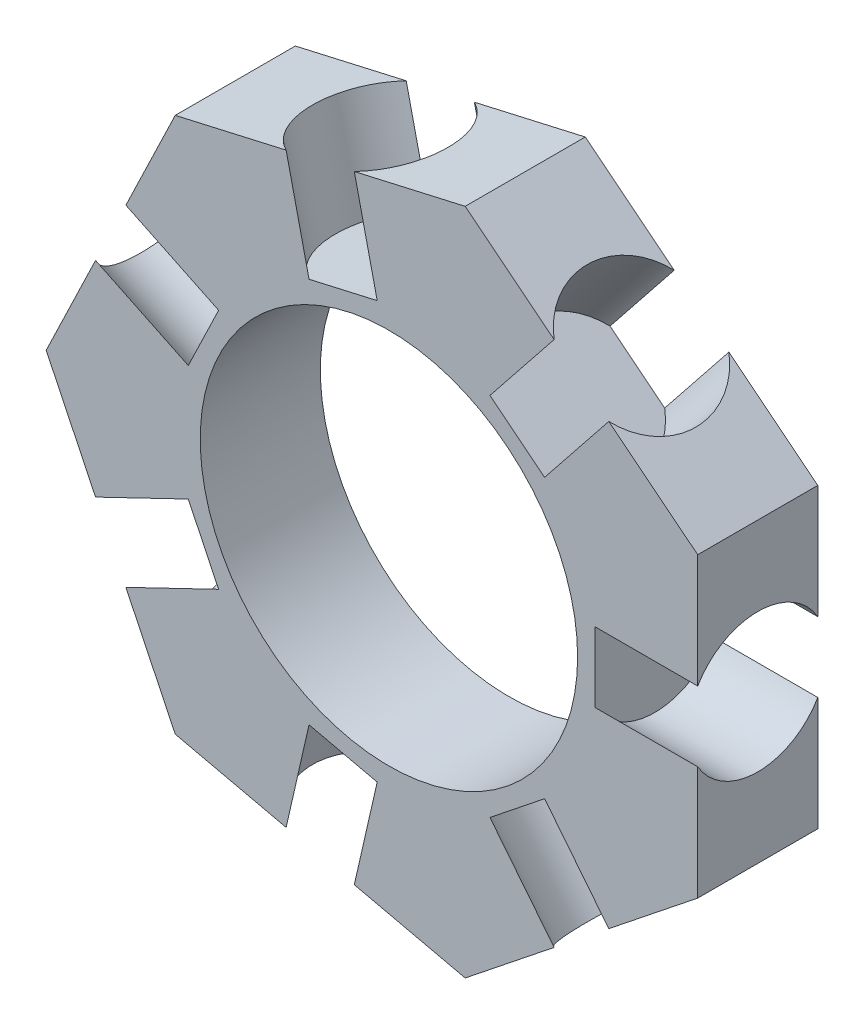
SolidWorks part; units mm, degrees
ref_plane "Top Plane" through (0, 0, 0) normal (0, 0, 1) x (1, 0, 0)
ref_plane "Right Plane" through (0, 0, 0) normal (0, 1, 0) x (1, 0, 0)
ref_plane "Front Plane" through (0, 0, 0) normal (1, 0, 0) x (0, 0, -1)
ref_axis "x-axis" through (-88.99, 0, 0) along (1, 0, 0)
ref_axis "y-axis" through (0, -55, 0) along (0, 1, 0)
ref_axis "z-axis" through (0, 0, 55) along (0, 0, -1)
sketch "Sketch1" plane through (0, 0, 0) normal (0, 0, 1) x (1, 0, 0)
  line L8 (-19.9785, 0) -> (0, 0) construction
  line L9 (-19.9785, 0) -> (-12.4564, -15.6198)
  line L10 (-12.4564, -15.6198) -> (4.4456, -19.4776)
  line L11 (4.4456, -19.4776) -> (18, -8.6683)
  line L12 (18, -8.6683) -> (18, 8.6683)
  line L13 (18, 8.6683) -> (4.4456, 19.4776)
  line L14 (4.4456, 19.4776) -> (-12.4564, 15.6198)
  line L15 (-12.4564, 15.6198) -> (-19.9785, 0)
  circle A0 centre (0, 0) radius 11
  circle A1 centre (0, 0) radius 18 construction
  circle A2 centre (0, 0) radius 19.9785 construction
  point P14 (1.5075, -10.8962)
  dimension "D1" = 22
  dimension "D2" = 7
extrude "Boss-Extrude1" add sketch "Sketch1" along normal mid plane 7
sketch "Sketch2" plane through (0.059, -18.4764, 0) normal (-0.2225, -0.9749, 0) x (-0.9749, 0.2225, 0)
  circle A0 centre (4.1689, 0) radius 4.05
  dimension "D1" = 8.1
extrude "Cut-Extrude3" cut sketch "Sketch2" against normal blind 6
pattern_circular "CirPattern1" count 7 over 360 about axis through (0, 0, 3.5) along (0, 0, 1) of "Cut-Extrude3"
